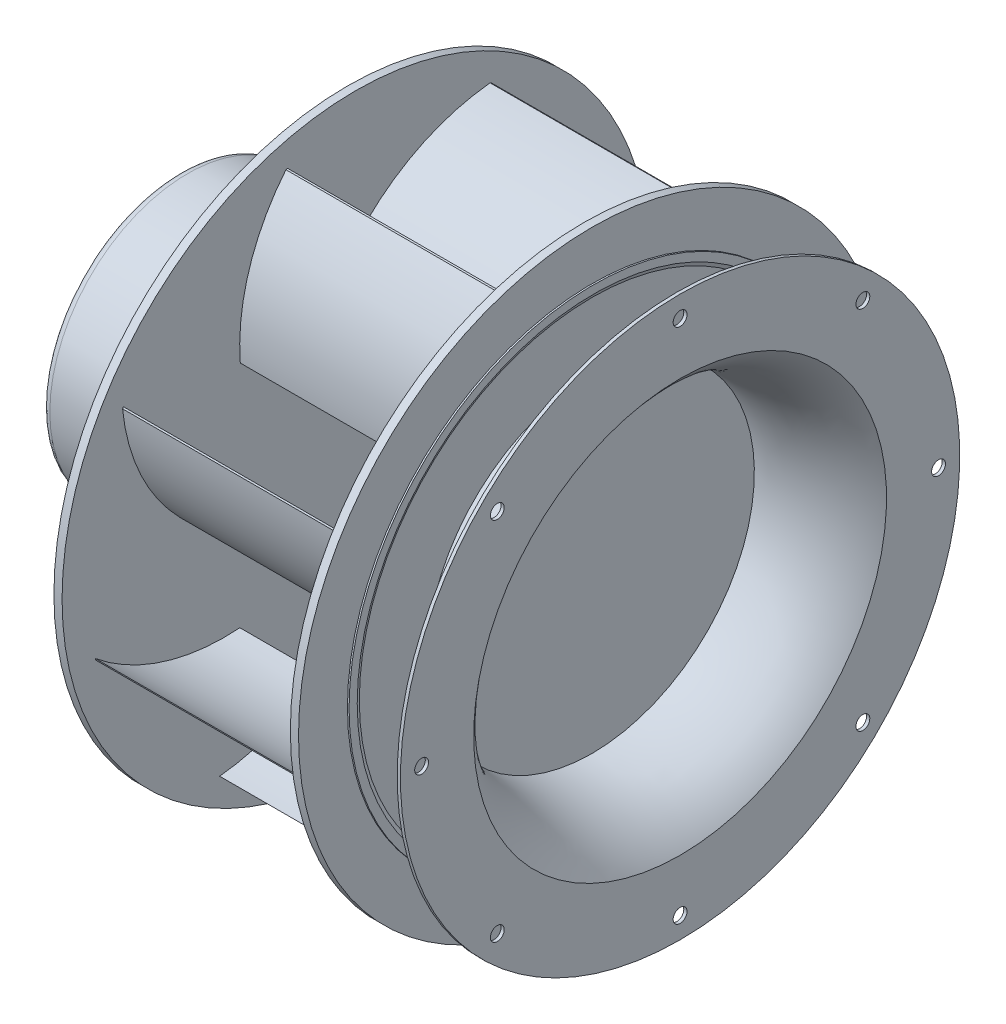
SolidWorks part; units mm, degrees
ref_plane "Front Plane" through (0, 0, 0) normal (0, 0, 1) x (1, 0, 0)
ref_plane "Top Plane" through (0, 0, 0) normal (0, 1, 0) x (1, 0, 0)
ref_plane "Right Plane" through (0, 0, 0) normal (1, 0, 0) x (0, 0, -1)
sketch "Sketch1" plane through (0, 0, 0) normal (0, 0, 1) x (1, 0, 0)
  line L0 (0, 0) -> (831.9083, 0) construction
  line L1 (0, 0) -> (0, 79.5)
  line L2 (5, 84.5) -> (56, 84.5)
  line L3 (56, 84.5) -> (56, 108.5)
  line L4 (56, 108.5) -> (69.9, 108.5)
  line L5 (69.9, 108.5) -> (69.9, 68.5)
  line L6 (69.9, 68.5) -> (74.9, 68.5)
  line L7 (74.9, 68.5) -> (74.9, 103.5)
  line L8 (74.9, 103.5) -> (84.9, 103.5)
  line L9 (84.9, 103.5) -> (84.9, 68.5)
  line L10 (84.9, 68.5) -> (103, 68.5)
  line L11 (103, 68.5) -> (103, 0)
  line L12 (103, 0) -> (0, 0)
  arc A0 (5, 84.5) -> (0, 79.5) centre (5, 79.5) ccw
  point P16 (0, 84.5)
  dimension "D10" = 5
  dimension "D1" = 84.5
  dimension "D2" = 24
  dimension "D3" = 56
  dimension "D4" = 40
  dimension "D5" = 35
  dimension "D6" = 5
  dimension "D7" = 13.9
  dimension "D8" = 10
  dimension "D9" = 47
revolve "Revolve1" add sketch "Sketch1" angle 360 about L0
sketch "Sketch2" plane through (103, 0, 0) normal (1, 0, 0) x (0, 0, -1)
  circle A0 centre (0, 0) radius 180
  dimension "D1" = 360
extrude "Extrude1" add sketch "Sketch2" along normal blind 5
sketch "Sketch9" plane through (103, 0, 0) normal (-1, 0, 0) x (0, 0, 1)
  circle A0 centre (0, 0) radius 175
  circle A1 centre (0, 0) radius 70
  circle A2 centre (0, 0) radius 180 construction
  dimension "D1" = 5
  dimension "D2" = 140
extrude "Extrude7" cut sketch "Sketch9" against normal blind 3
ref_plane "Plane1" through (248, 0, 0) normal (1, 0, 0) x (0, 0, -1)
sketch "Sketch3" plane through (248, 0, 0) normal (1, 0, 0) x (0, 0, -1)
  circle A0 centre (0, 0) radius 180
  dimension "D1" = 360
extrude "Extrude2" add sketch "Sketch3" along normal blind 5 separate body
sketch "Sketch4" plane through (108, 0, 0) normal (1, 0, 0) x (0, 0, -1)
  line L0 (0, 0) -> (0, 165) construction
  line L1 (0, 0) -> (90, 155.8846) construction
  line L2 (0, 100) -> (0.866, 99.5)
  line L3 (82.5, 142.8942) -> (83.366, 142.3942)
  circle A0 centre (0, 0) radius 165 construction
  circle A1 centre (0, 0) radius 180 construction
  circle A2 centre (0, 0) radius 100 construction
  arc A3 (0, 100) -> (82.5, 142.8942) centre (94.776, 18.4985) cw
  arc A4 (0.866, 99.5) -> (83.366, 142.3942) centre (95.6421, 17.9985) cw
  dimension "D1" = 15
  dimension "D2" = 200
  dimension "D6" = 125
  dimension "D7" = 125
  dimension "D3" = 30
  dimension "D4" = 60
  dimension "D5" = 1
extrude "Extrude3" add sketch "Sketch4" along normal up to surface (145 mm away) up to face at (253, 0, -180)
ref_axis "Axis1" through (253.5503, 0, 0) along (-1, 0, 0)
pattern_circular "CirPattern1" count 8 over 360 about axis through (253.5503, 0, 0) along (-1, 0, 0) of "Extrude3"
sketch "Sketch5" plane through (0, 0, 0) normal (0, 0, 1) x (1, 0, 0)
  line L0 (0, 0) -> (527.2916, 0) construction
  line L1 (253.5503, 0) -> (75.411, 0) construction
  line L2 (253, 150) -> (254, 150)
  line L3 (254, 150) -> (254, 145)
  line L4 (253, 150) -> (253, 145)
  line L5 (251, 102.5) -> (251, 101.5)
  line L6 (56, 108.5) -> (56, -108.5) construction
  line L7 (253, -180) -> (253, 180) construction
  arc A0 (254, 145) -> (251, 102.5) centre (308.4517, 119.8005) ccw
  arc A1 (253, 145) -> (251, 101.5) centre (307.8511, 120.6821) ccw
  dimension "D7" = 60
  dimension "D8" = 60
  dimension "D1" = 101.5
  dimension "D2" = 1
  dimension "D3" = 1
  dimension "D4" = 5
  dimension "D5" = 150
  dimension "D6" = 195
revolve "Revolve2" add sketch "Sketch5" angle 360 about L0
ref_plane "Plane3" through (307, 0, 0) normal (1, 0, 0) x (0, 0, -1)
sketch "Sketch6" plane through (0, 0, 0) normal (0, 0, 1) x (1, 0, 0)
  line L0 (307, 171.5) -> (305, 171.5)
  line L1 (307, -251.35) -> (307, 251.35) construction
  line L2 (305, 171.5) -> (305, 126.6)
  line L3 (0, 0) -> (615.1417, 0) construction
  line L4 (0, 84.5) -> (0, -84.5) construction
  line L5 (253.5503, 0) -> (75.411, 0) construction
  line L6 (307, 171.5) -> (307, 126.6)
  line L7 (248.5, 101.5) -> (252.5, 101.5)
  line L8 (248.5, 101.5) -> (248.5, 99.5)
  line L9 (248.5, 99.5) -> (252.5, 99.5)
  arc A0 (252.5, 101.5) -> (305, 126.6) centre (251.2884, 171.4895) ccw
  arc A1 (252.5, 99.5) -> (307, 126.6) centre (251.6827, 169.4952) ccw
  dimension "D7" = 70
  dimension "D8" = 70
  dimension "D1" = 171.5
  dimension "D2" = 2
  dimension "D3" = 126.6
  dimension "D4" = 58.5
  dimension "D5" = 101.5
  dimension "D6" = 4
revolve "Revolve3" add sketch "Sketch6" angle 360 about L3
sketch "Sketch7" plane through (307, 0, 0) normal (1, 0, 0) x (0, 0, -1)
  line L0 (0, 0) -> (0, 158.5) construction
  circle A0 centre (0, 0) radius 158.5 construction
  circle A1 centre (0, 158.5) radius 4.25
  dimension "D1" = 317
  dimension "D2" = 8.5
extrude "Extrude5" cut sketch "Sketch7" against normal blind 5
pattern_circular "CirPattern2" count 8 over 360 about axis through (253.5503, 0, 0) along (-1, 0, 0) of "Extrude5"
sketch "Sketch8" plane through (0, 0, 0) normal (1, 0, 0) x (0, 0, -1)
  line L0 (0, 0) -> (0, 95) construction
  circle A0 centre (0, 0) radius 95 construction
  circle A1 centre (0, 95) radius 5
  dimension "D1" = 190
  dimension "D2" = 10
extrude "Extrude6" cut sketch "Sketch8" along normal up to surface (69.9 mm away) up to face at (69.9, 0, 108.5)
pattern_circular "CirPattern3" count 4 over 360 about axis through (253.5503, 0, 0) along (-1, 0, 0) of "Extrude6"
